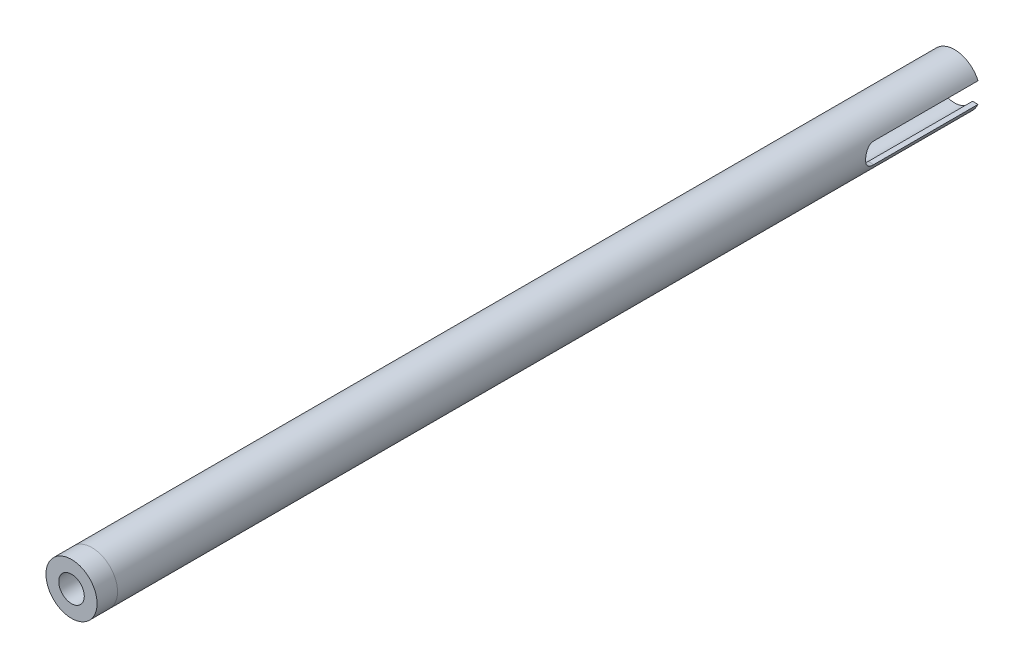
SolidWorks part; units mm, degrees
material "AISI 4130 Steel, annealed at 865C"
ref_plane "Front Plane" through (0, 0, 0) normal (0, 0, 1) x (1, 0, 0)
ref_plane "Top Plane" through (0, 0, 0) normal (0, 1, 0) x (1, 0, 0)
ref_plane "Right Plane" through (0, 0, 0) normal (1, 0, 0) x (0, 0, -1)
sketch "Axis" plane through (0, 0, 0) normal (0, 1, 0) x (1, 0, 0)
  line L0 (0, 0) -> (0, 274.208) construction
  line L1 (0, 0) -> (0, -28.575) construction
  line L2 (0, 274.208) -> (-7.9375, 274.208) construction
  line L4 (0, 295.0656) -> (-10.3187, 267.9508) construction
  dimension "D1" = 28.575
  dimension "D2" = 7.9375
sketch "Sketch1" plane through (0, 0, 0) normal (0, 0, 1) x (1, 0, 0)
  line L0 (-7.9375, 0) -> (7.9375, 0) construction
  line L1 (-7.2748, 3.175) -> (7.2748, 3.175)
  line L2 (-7.2748, -3.175) -> (7.2748, -3.175)
  circle A0 centre (0, 0) radius 7.9375
  circle A1 centre (0, 0) radius 6.4135
  circle A2 centre (0, 0) radius 3.9688
  dimension "D1" = 15.875
  dimension "D3" = 7.9375
  dimension "D2" = 1.524
  dimension "D4" = 6.35
extrude "Threaded insert 1-1" add sketch "Sketch1" against normal blind 6.35 contours A2 L1 A1 | A1 L1 A0 | A2 L0 A1 L1 | A1 L0 A0 L1 | L0 A1 L2 A0 | L0 A2 L2 A1 | A2 L2 A1 | A1 L2 A0 | L0 A1 L2 A2 | L0 A0 L2 A1 | A0 L0 A1 L1 | A1 L0 A2 L1 region at (4.7887, 1.6543, 0) region at (4.7887, -1.6543, 0) region at (6.9234, 1.6163, 0) region at (6.9234, -1.6163, 0) region at (-4.7887, -1.6543, 0) region at (-4.7887, 1.6543, 0) region at (0, 4.6159, 0) region at (0, -4.6159, 0) region at (0, 6.5666, 0) region at (6.4237, -3.3281, 0) region at (-6.9234, -1.6163, 0) region at (-6.9234, 1.6163, 0)
extrude "Threaded insert 1-2" add sketch "Sketch1<3>" against normal blind 9.525 from surface contours A2 L1 A1 | A2 L0 A1 L1 | L0 A2 L2 A1 | A2 L2 A1 | L0 A1 L2 A2 | A1 L0 A2 L1 region at (4.7887, 1.6543, 0) region at (4.7887, -1.6543, 0) region at (-4.7887, -1.6543, 0) region at (-4.7887, 1.6543, 0) region at (0, 4.6159, 0) region at (0, -4.6159, 0) starting at face at (7.9375, 0, -6.35)
sketch "Sketch1<3>" plane through (0, 0, 0) normal (0, 0, 1) x (1, 0, 0) same geometry as "Sketch1"
extrude "A-arm tube" add sketch "Sketch1<4>" against normal up to vertex (274.208 mm away) from surface separate body contours A1 L1 A0 | A1 L0 A0 L1 | L0 A1 L2 A0 | A1 L2 A0 | L0 A0 L2 A1 | A0 L0 A1 L1 region at (6.9234, 1.6163, 0) region at (6.9234, -1.6163, 0) region at (0, 6.5666, 0) region at (6.4237, -3.3281, 0) region at (-6.9234, -1.6163, 0) region at (-6.9234, 1.6163, 0) up to point (0, 0, -274.208) starting at face at (6.4135, 0, -6.35)
sketch "Sketch1<4>" plane through (0, 0, 0) normal (0, 0, 1) x (1, 0, 0) same geometry as "Sketch1"
extrude "Apex slot" cut sketch "Sketch1<5>" along normal blind 35.56 from surface contours A0 L0 A1 L1 | L0 A0 L2 A1 | A1 L0 A0 L1 | L0 A1 L2 A0 region at (6.9234, 1.6163, 0) region at (6.9234, -1.6163, 0) region at (-6.9234, -1.6163, 0) region at (-6.9234, 1.6163, 0) starting at face at (6.4135, 0, -274.208)
sketch "Sketch1<5>" plane through (0, 0, 0) normal (0, 0, 1) x (1, 0, 0) same geometry as "Sketch1"
fillet "Fillet1" radius 3.175 4 edges at (-6.4237, 3.175, -238.648) (-6.4237, -3.175, -238.648) (6.4237, -3.175, -238.648) (6.4237, 3.175, -238.648)
equation "\"tube diameter\"= 5 / 8"
equation "\"tube thickness\"= .06"
equation "\"apex thickness\"= .25"
equation "\"tube slot\"= 1.4"
equation "\"D1@Sketch1\"=\"tube diameter\""
equation "\"D2@Sketch1\"=\"tube thickness\""
equation "\"threaded insert hole\"= .3125"
equation "\"D3@Sketch1\"=\"threaded insert hole\""
equation "\"D4@Sketch1\"=\"apex thickness\""
equation "\"D1@Apex slot\" = \"tube slot\""
equation "\"D1@Fillet1\"=\"apex thickness\"/2"
